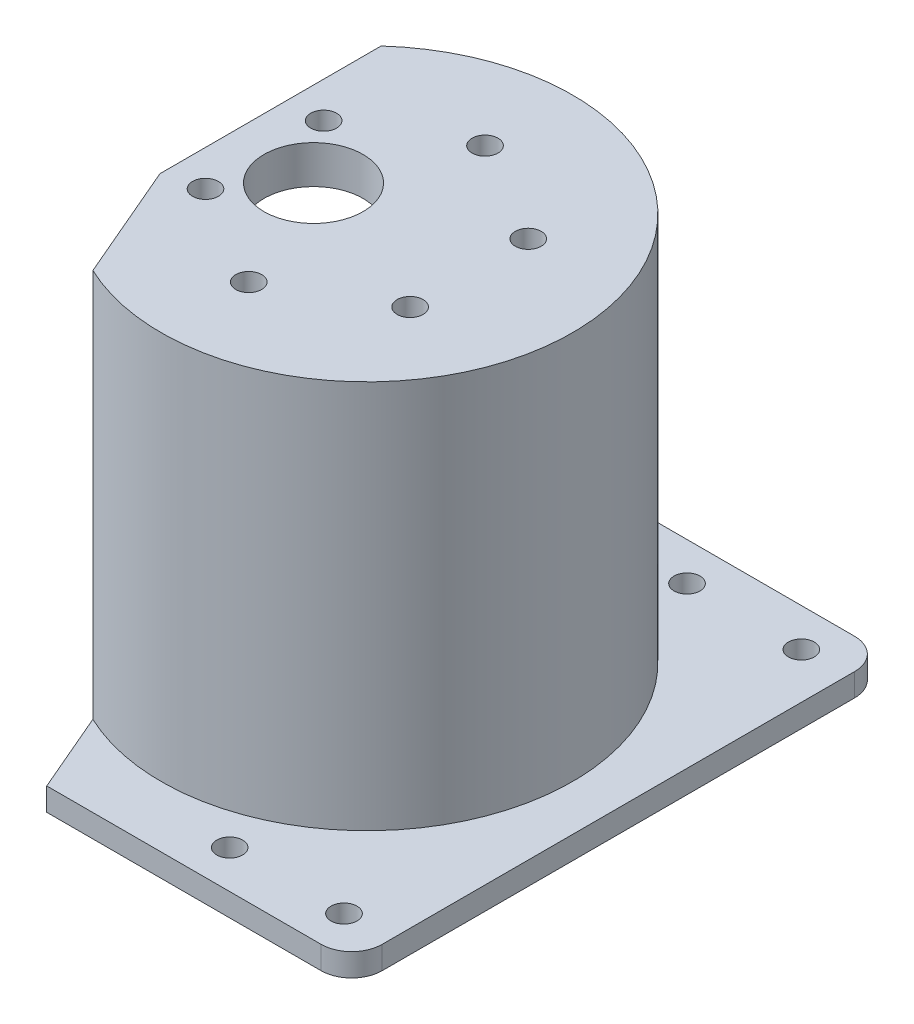
SolidWorks part; units mm, degrees
ref_plane "Płaszczyzna przednia" through (0, 0, 0) normal (0, 0, 1) x (1, 0, 0)
ref_plane "Płaszczyzna górna" through (0, 0, 0) normal (0, 1, 0) x (1, 0, 0)
ref_plane "Płaszczyzna prawa" through (0, 0, 0) normal (1, 0, 0) x (0, 0, -1)
sketch "Szkic1" plane through (0, 0, 0) normal (0, 1, 0) x (1, 0, 0)
  line L0 (-27.5, 20) -> (-12.5, 20)
  line L1 (-23.5, 35) -> (23.5, 35)
  line L2 (-27.5, 31) -> (-27.5, 20)
  line L3 (-23.5, -35) -> (23.5, -35)
  line L4 (27.5, 31) -> (27.5, -31)
  line L5 (-27.5, 35) -> (27.5, -35) construction
  line L6 (-27.5, -35) -> (27.5, 35) construction
  line L7 (-27.5, -20) -> (-12.5, -20)
  line L8 (-27.5, -20) -> (-27.5, -31)
  arc A0 (-27.5, -31) -> (-23.5, -35) centre (-23.5, -31) ccw
  arc A1 (23.5, -35) -> (27.5, -31) centre (23.5, -31) ccw
  arc A2 (23.5, 35) -> (27.5, 31) centre (23.5, 31) cw
  arc A3 (-23.5, 35) -> (-27.5, 31) centre (-23.5, 31) ccw
  arc A4 (-11.38, -20.16) -> (-11.38, 20.16) centre (-5.5, 0) ccw
  arc A5 (-12.5, -20) -> (-11.38, -20.16) centre (-12.5, -24) cw
  arc A6 (-12.5, 20) -> (-11.38, 20.16) centre (-12.5, 24) ccw
  point P0 (0, 0)
  dimension "D1" = 4
  dimension "D2" = 40
  dimension "D3" = 4
  dimension "D5" = 21
  dimension "D4" = 70
  dimension "D6" = 55
  dimension "D7" = 33
extrude "Dodanie-wyciągnięcie1" add sketch "Szkic1" along normal blind 3
sketch "Szkic2" plane through (0, 3, 0) normal (0, 1, 0) x (1, 0, 0)
  line L0 (-12.5, -20) -> (-27.5, -20) construction
  line L1 (-27.5, 20) -> (-12.5, 20) construction
  line L2 (-12.5, -20) -> (-23.6384, -20)
  line L3 (-23.6384, 20) -> (-12.5, 20)
  arc A0 (-11.38, -20.16) -> (-12.5, -20) centre (-12.5, -24) ccw construction
  arc A1 (-12.5, 20) -> (-11.38, 20.16) centre (-12.5, 24) ccw construction
  arc A2 (-11.38, -20.16) -> (-11.38, 20.16) centre (-5.5, 0) ccw construction
  arc A3 (-11.38, -20.16) -> (-12.5, -20) centre (-12.5, -24) ccw
  arc A4 (-12.5, 20) -> (-11.38, 20.16) centre (-12.5, 24) ccw
  arc A5 (-11.38, -20.16) -> (-11.38, 20.16) centre (-5.5, 0) ccw
  arc A6 (-23.6384, -20) -> (-23.6384, 20) centre (-5.5, 0) ccw
  dimension "D1" = 54
extrude "Dodanie-wyciągnięcie2" add sketch "Szkic2" along normal blind 51
sketch "Szkic3" plane through (0, 54, 0) normal (0, 1, 0) x (1, 0, 0)
  line L0 (-23.6384, 20) -> (-23.6384, -20)
  arc A0 (-23.6384, -20) -> (-23.6384, 20) centre (-5.5, 0) ccw construction
  arc A1 (-23.6384, -20) -> (-23.6384, 20) centre (-5.5, 0) ccw
extrude "Dodanie-wyciągnięcie3" add sketch "Szkic3" against normal blind 5
sketch "Szkic4" plane through (0, 3, 0) normal (0, 1, 0) x (1, 0, 0)
  line L0 (-23.5, -35) -> (23.5, -35) construction
  line L1 (-27.5, -20) -> (-27.5, -31) construction
  circle A0 centre (-21.5, -30) radius 1.7
  circle A1 centre (21.5, -30) radius 1.7
  circle A2 centre (21.5, 30) radius 1.7
  circle A3 centre (-21.5, 30) radius 1.7
  circle A4 centre (6.5, -30) radius 1.7
  circle A5 centre (6.5, 30) radius 1.7
  dimension "D1" = 3.4
  dimension "D6" = 15
  dimension "D7" = 43
  dimension "D8" = 60
  dimension "D2" = 5
  dimension "D3" = 6
  dimension "D4" = 2
  dimension "D5" = 2
extrude "Wytnij-wyciągnięcie1" cut sketch "Szkic4" against normal blind 5
sketch "Szkic5" plane through (0, 54, 0) normal (0, 1, 0) x (1, 0, 0)
  line L0 (-5.5, 0) -> (-5.5, -15.5) construction
  circle A0 centre (-12.5, 0) radius 6.5
  arc A1 (-23.6384, -20) -> (-23.6384, 20) centre (-5.5, 0) ccw construction
  circle A2 centre (-5.5, -15.5) radius 1.7
  circle A3 centre (-18.9234, -7.75) radius 1.7
  circle A4 centre (-18.9234, 7.75) radius 1.7
  circle A5 centre (-5.5, 15.5) radius 1.7
  circle A6 centre (7.9234, 7.75) radius 1.7
  circle A7 centre (7.9234, -7.75) radius 1.7
  point P23 (-5.5, 0)
  dimension "D1" = 7
  dimension "D2" = 13
  dimension "D3" = 3.4
  dimension "D4" = 15.5
  dimension "D5" = 6
extrude "Wytnij-wyciągnięcie2" cut sketch "Szkic5" against normal blind 5
sketch "Szkic6" plane through (0, 3, 0) normal (0, 1, 0) x (1, 0, 0)
  line L0 (-27.5, 0) -> (-12.5, -35)
  line L1 (-23.5, -35) -> (23.5, -35) construction
  line L2 (-12.5, -35) -> (-27.5, -35)
  line L3 (-27.5, -35) -> (-27.5, 0)
  line L4 (27.5, -31) -> (27.5, 31) construction
  point P5 (0, 0)
  dimension "D1" = 15
  dimension "D2" = 35
  dimension "D3" = 55
extrude "Wytnij-wyciągnięcie3" cut sketch "Szkic6" along normal up to surface (51 mm away) and the other way blind 10 up to face at (7.9234, 54, 9.45)
